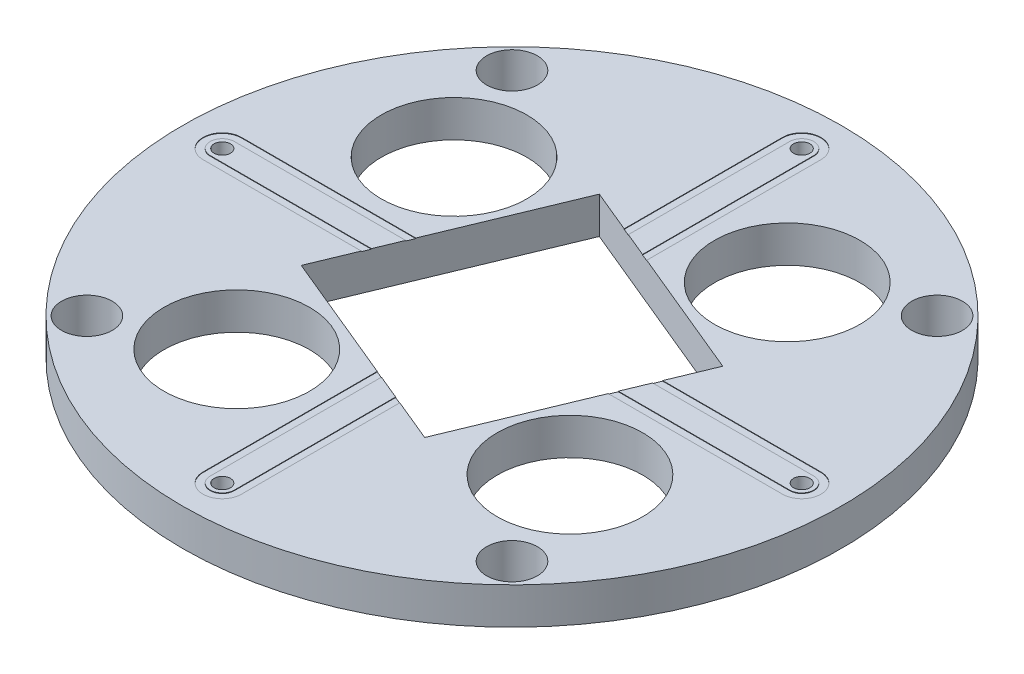
SolidWorks part; units mm, degrees
material "Ceramic Porcelain"
ref_plane "Front Plane" through (0, 0, 0) normal (0, 0, 1) x (1, 0, 0)
ref_plane "Top Plane" through (0, 0, 0) normal (0, 1, 0) x (1, 0, 0)
ref_plane "Right Plane" through (0, 0, 0) normal (1, 0, 0) x (0, 0, -1)
ref_axis "Y Axis" through (0, 0.0762, 0) along (0, -1, 0)
sketch "Boday Sketch" plane through (0, 0, 0) normal (0, 1, 0) x (1, 0, 0)
  circle A0 centre (0, 0) radius 11.557
  dimension "D1" = 23.114
extrude "Body" add sketch "Boday Sketch" against normal blind 1.27
sketch "Copper Sketch" plane through (0, 0, 0) normal (0, 1, 0) x (1, 0, 0)
  circle A0 centre (0, 0) radius 11.557
  dimension "D1" = 23.114
extrude "Copper" add sketch "Copper Sketch" along normal blind 0.0175
sketch "Screw Position" plane through (0, 0, 0) normal (0, 1, 0) x (1, 0, 0)
  point P0 (-7.4536, 7.4536)
  point P1 (0, 0)
  point P3 (0, 0)
sketch "IO Hole Positions" plane through (0, 0, 0) normal (0, 1, 0) x (1, 0, 0)
  point P0 (-3.8881, 9.3866)
  point P1 (3.8881, 9.3866)
  point P5 (9.3866, 3.8881)
  point P6 (9.3866, -3.8881)
  point P7 (3.8881, -9.3866)
  point P8 (-3.8881, -9.3866)
  point P9 (-9.3866, -3.8881)
  point P10 (-9.3866, 3.8881)
  point P11 (0, 0)
  dimension "D2" = 8
sketch "Gap" plane through (0, 0, 0) normal (0, 1, 0) x (1, 0, 0)
  line L2 (0.675, 0) -> (0.675, 10.16)
  line L4 (-0.675, 10.16) -> (-0.675, 0)
  line L5 (-0.675, 0) -> (0.675, 0)
  arc A2 (0.675, 10.16) -> (-0.675, 10.16) centre (0, 10.16) ccw
  point P0 (0.675, 0)
  dimension "D2" = 10.16
sketch "Center Sketch" plane through (0, 0, 0) normal (0, 1, 0) x (1, 0, 0)
  line L0 (0.425, 0) -> (0.425, 10.16)
  line L3 (-0.425, 10.16) -> (-0.425, 0)
  line L4 (-0.425, 0) -> (0.425, 0)
  arc A1 (0.425, 10.16) -> (-0.425, 10.16) centre (0, 10.16) ccw
  point P0 (0.425, 0)
  point P3 (0.425, 10.16)
  dimension "D2" = 10.16
hole_wizard "#0 Clearance Hole1" positions "Sketch23" profile "Sketch24" hole size "#0" standard "ANSI Inch" end condition through all
sketch "Sketch23" plane through (0, 0.0175, 0) normal (0, 1, 0) x (-1, 0, 0)
  point P2 (7.4536, -7.4536)
sketch "Sketch24" plane through (-7.4536, 0.0175, -7.4536) normal (1, 0, 0) x (0, 0, 1)
  line L0 (0, 0) -> (0, 1.2875)
  line L1 (0, 1.2875) -> (0.889, 1.2875)
  line L2 (0.889, 1.2875) -> (0.889, 0)
  line L5 (0.889, 0) -> (0, 0)
  line L11 (0, -6.35) -> (0, 107.95) construction
  dimension "Thru Hole Dia." = 1.778
  dimension "Thru Hole Depth" = 1.2875
pattern_circular "Screw Holes" count 4 over 360 about axis through (0, 0.0762, 0) along (0, -1, 0) of "#0 Clearance Hole1"
extrude "Gap Cut" cut sketch "Gap" along normal through all
extrude "Center" add sketch "Center Sketch" along normal blind 0.0175 separate body
sketch "IO Hole Sketch" plane through (0, 0, 0) normal (0, 1, 0) x (1, 0, 0)
  circle A0 centre (0, 10.16) radius 0.287
  dimension "D1" = 0.574
extrude "IO Hole" cut sketch "IO Hole Sketch" against normal through all and the other way through all
pattern_circular "Gap Cuts" count 4 over 360 about axis through (0, 0.0762, 0) along (0, -1, 0) of "Gap Cut"
pattern_circular "Centers" count 4 over 360 about axis through (0, 0.0762, 0) along (0, -1, 0) of "Center"
pattern_circular "IO Holes" count 4 over 360 about axis through (0, 0.0762, 0) along (0, -1, 0) of "IO Hole"
sketch "Pocket Sketch" plane through (0, 0, 0) normal (0, 1, 0) x (1, 0, 0)
  line L1 (-5.2263, -2.1648) -> (2.1648, -5.2263)
  line L2 (-5.2263, -2.1648) -> (-2.1648, 5.2263)
  line L3 (-2.1648, 5.2263) -> (5.2263, 2.1648)
  line L4 (2.1648, -5.2263) -> (5.2263, 2.1648)
  line L5 (-5.2263, -2.1648) -> (5.2263, 2.1648) construction
  line L6 (-2.1648, 5.2263) -> (2.1648, -5.2263) construction
  point P0 (0, 0)
  dimension "D2" = 8
  dimension "D1" = 8
extrude "Pocket" cut sketch "Pocket Sketch" against normal through all and the other way through all
sketch "Posts" plane through (0, 0, 0) normal (0, 1, 0) x (1, 0, 0)
  circle A9 centre (3.81, 5.842) radius 2.5527
  point P5 (-3.8043, 3.5769)
  point P9 (13.1911, 4.6727)
  dimension "D3" = 5.1054
  dimension "D1" = 3.81
  dimension "D2" = 5.842
extrude "Post Cut" cut sketch "Posts" against normal through all and the other way through all
pattern_circular "Post Cuts" count 4 over 360 about axis through (0, 0.0762, 0) along (0, -1, 0) of "Post Cut"
equation "\"mount_d\"= 0.91in"
equation "\"dieletric_h\"= 0.05in"
equation "\"D1@Boday Sketch\" = \"mount_d\""
equation "\"D1@Body\" = \"dieletric_h\""
equation "\"screw_inner_r\"= 0.415in"
equation "\"io_r\"= 0.4in"
equation "\"D1@Screw Position\" = \"screw_inner_r\""
equation "\"D1@IO Hole Positions\" = \"io_r\""
equation "\"io_hole_d\"= 0.574mm"
equation "\"D1@IO Hole Sketch\" = \"io_hole_d\""
equation "\"W\"= 0.85mm"
equation "\"G\"= 0.25mm"
equation "\"copper_t\"= 17.5um"
equation "\"silicon_size\"= 8mm"
equation "\"D1@Center\" = \"copper_t\""
equation "\"D1@Copper\"=\"copper_t\""
equation "\"D1@Pocket Sketch\" = \"silicon_size\""
equation "\"D2@Pocket Sketch\" = \"silicon_size\""
equation "\"post_x\" = 0.15in"
equation "\"post_z\"= 0.23in"
equation "\"post_d\" = 0.201in"
equation "\"D1@Posts\"=\"post_x\""
equation "\"D2@Posts\"=\"post_z\""
equation "\"D3@Posts\"=\"post_d\""
equation "\"D1@Gap\"=\"W\" / 2 + \"G\""
equation "\"D2@Gap\"=\"io_r\""
equation "\"D1@Center Sketch\"=\"W\" / 2"
equation "\"D2@Center Sketch\"=\"io_r\""
